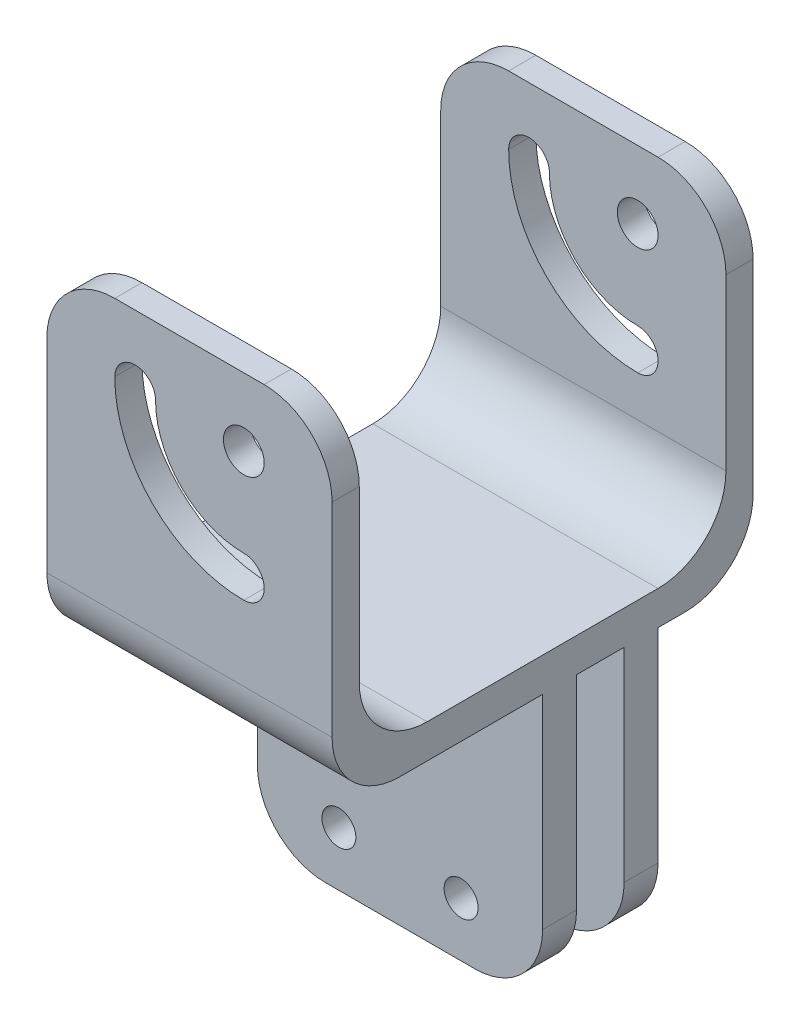
SolidWorks part; units mm, degrees
other "Marcação1"
sketch "Esboço5" plane through (0, 50, 68.25) normal (-0.797, 0.1637, 0.5813) x (0.5636, -0.1442, 0.8134)
ref_plane "Plano frontal" through (0, 0, 0) normal (0, 0, 1) x (1, 0, 0)
ref_plane "Plano superior" through (0, 0, 0) normal (0, 1, 0) x (1, 0, 0)
ref_plane "Plano direito" through (0, 0, 0) normal (1, 0, 0) x (0, 0, -1)
sketch "Esboço1" plane through (0, 0, 0) normal (0, 0, 1) x (1, 0, 0)
  line L0 (0, 0) -> (0, 50)
  line L1 (0, 50) -> (42, 50)
  line L2 (42, 50) -> (42, 0)
  line L3 (42, 0) -> (0, 0)
  line L4 (29, 40) -> (29, 37) construction
  circle A0 centre (29, 40) radius 3
  arc A2 (29, 24) -> (13, 40) centre (29, 40) cw construction
  arc A3 (10, 40) -> (29, 21) centre (29, 40) ccw
  arc A4 (16, 40) -> (29, 27) centre (29, 40) ccw
  arc A5 (16, 40) -> (10, 40) centre (13, 40) ccw
  arc A6 (29, 21) -> (29, 27) centre (29, 24) ccw
  point P10 (17.6863, 28.6863)
  dimension "D3" = 6
  dimension "D5" = 16
  dimension "D6" = 13
  dimension "D1" = 29
  dimension "D2" = 50
  dimension "D4" = 13
extrude "Ressalto-extrusão2" add sketch "Esboço1" along normal blind 62
sketch "Esboço3" plane through (0, 50, 0) normal (0, 1, 0) x (1, 0, 0)
  line L0 (0, -58) -> (42, -58)
  line L1 (0, -62) -> (0, 0) construction
  line L2 (42, -62) -> (42, 0) construction
  line L3 (42, -58) -> (42, -4)
  line L4 (42, -4) -> (0, -4)
  line L5 (0, -4) -> (0, -58)
  line L6 (42, 0) -> (0, 0) construction
  dimension "D1" = 4
  dimension "D2" = 4
extrude "Corte-extrusão1" cut sketch "Esboço3" against normal blind 45
sketch "Esboço7" plane through (0, 0, 0) normal (0, -1, 0) x (1, 0, 0)
  line L0 (0, 14) -> (42, 14)
  line L1 (0, 62) -> (0, 0) construction
  line L2 (42, 62) -> (42, 0) construction
  line L3 (42, 14) -> (42, 19)
  line L4 (42, 19) -> (0, 19)
  line L5 (0, 19) -> (0, 14)
  line L6 (0, 26) -> (42, 26)
  line L7 (42, 26) -> (42, 31)
  line L8 (42, 31) -> (0, 31)
  line L9 (0, 31) -> (0, 26)
  dimension "D1" = 5
  dimension "D2" = 5
  dimension "D3" = 7
extrude "Ressalto-extrusão3" add sketch "Esboço7" along normal blind 40
sketch "Esboço10" plane through (0, 0, 14) normal (0, 0, -1) x (-1, 0, 0)
  line L0 (-42, -40) -> (-42, 0) construction
  line L1 (0, -40) -> (0, 0) construction
  line L2 (0, -40) -> (-42, -40) construction
  circle A5 centre (-30, -32) radius 2.5
  circle A6 centre (-12, -32) radius 2.5
  dimension "D7" = 5
  dimension "D8" = 5
  dimension "D2" = 12
  dimension "D3" = 12
  dimension "D10" = 18
  dimension "D11" = 8
extrude "Corte-extrusão2" cut sketch "Esboço10" against normal through all
fillet "Filete1" radius 10 12 edges at (21, 5, 4) (0, 50, 2) (42, 50, 2) (21, 5, 58) (21, 0, 62) (21, 0, 0) (42, -40, 28.5) (42, -40, 16.5) (0, -40, 16.5) (0, -40, 28.5) (0, 50, 60) (42, 50, 60)
